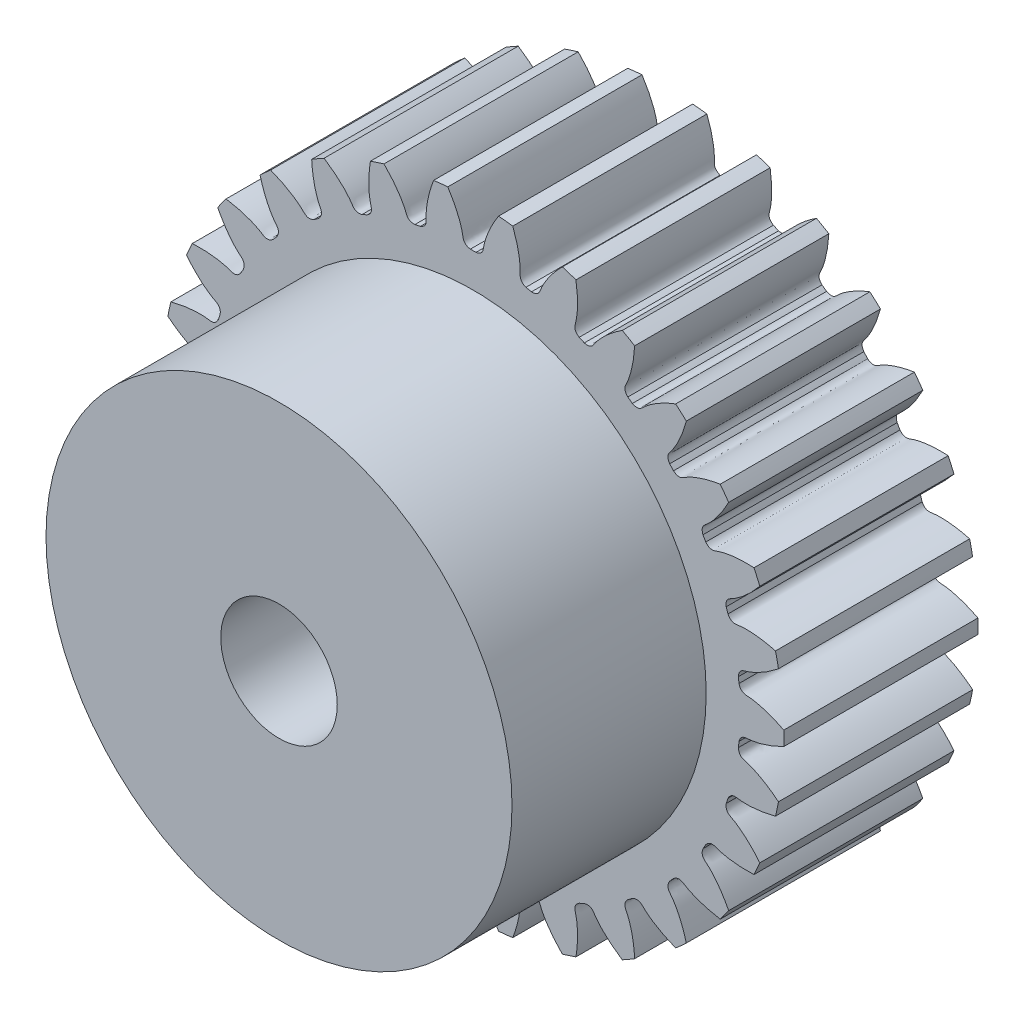
SolidWorks part; units mm, degrees
ref_plane "前视基准面" through (0, 0, 0) normal (0, 0, 1) x (1, 0, 0)
ref_plane "上视基准面" through (0, 0, 0) normal (0, 1, 0) x (1, 0, 0)
ref_plane "右视基准面" through (0, 0, 0) normal (1, 0, 0) x (0, 0, -1)
sketch "草图1" plane through (0, 0, 0) normal (0, 0, 1) x (1, 0, 0)
  circle A0 centre (0, 0) radius 8
extrude "凸台-拉伸1" add sketch "草图1" along normal blind 5
ref_axis "基准轴1" through (0, 0, 5) along (0, 0, -1)
sketch "草图2" plane through (0, 0, 0) normal (0, 0, 1) x (1, 0, 0)
  line L0 (0, 0) -> (0, 8) construction
  circle A0 centre (0, 0) radius 8 construction
  arc A1 (0.0728, 6.8746) -> (-0.0728, 6.8746) centre (0, 0) ccw
  arc A2 (1.6832, 9.0953) -> (-1.6832, 9.0953) centre (0, 0) ccw
  spline S0 degree 3 poles (0.0728, 6.8746) (0.2541, 6.9065) (0.2552, 7.0236) (0.2795, 7.1443) (0.285, 7.1691) (0.2916, 7.1965) (0.2995, 7.2264) (0.3088, 7.259) (0.3196, 7.294) (0.3319, 7.3315) (0.3459, 7.3714) (0.3617, 7.4137) (0.3794, 7.4582) (0.3991, 7.505) (0.4208, 7.554) (0.4447, 7.605) (0.4709, 7.6581) (0.4994, 7.7132) (0.5303, 7.7702) (0.5638, 7.829) (0.5999, 7.8895) (0.6387, 7.9517) (0.6803, 8.0155) (0.7247, 8.0807) (0.772, 8.1474) (0.8224, 8.2154) (0.8758, 8.2845) (0.9324, 8.3548) (0.9921, 8.4261) (1.0552, 8.4983) (1.1215, 8.5713) (1.1913, 8.6451) (1.2645, 8.7194) (1.3411, 8.7942) (1.4213, 8.8694) (1.5345, 8.9713) (1.6227, 9.046) (1.6832, 9.0953) knots 0 0 0 0 0.115324 0.123413 0.132512 0.142623 0.153745 0.165878 0.179022 0.193177 0.208343 0.22452 0.241708 0.259907 0.279117 0.299338 0.320571 0.342814 0.366068 0.390334 0.41561 0.441898 0.469196 0.497506 0.526827 0.557158 0.588501 0.620855 0.65422 0.688595 0.723982 0.76038 0.797789 0.836209 0.87564 0.916083 1 1 1 1
  spline S1 degree 3 poles (-0.0728, 6.8746) (-0.2541, 6.9065) (-0.2552, 7.0236) (-0.2795, 7.1443) (-0.285, 7.1691) (-0.2916, 7.1965) (-0.2995, 7.2264) (-0.3088, 7.259) (-0.3196, 7.294) (-0.3319, 7.3315) (-0.3459, 7.3714) (-0.3617, 7.4137) (-0.3794, 7.4582) (-0.3991, 7.505) (-0.4208, 7.554) (-0.4447, 7.605) (-0.4709, 7.6581) (-0.4994, 7.7132) (-0.5303, 7.7702) (-0.5638, 7.829) (-0.5999, 7.8895) (-0.6387, 7.9517) (-0.6803, 8.0155) (-0.7247, 8.0807) (-0.772, 8.1474) (-0.8224, 8.2154) (-0.8758, 8.2845) (-0.9324, 8.3548) (-0.9921, 8.4261) (-1.0552, 8.4983) (-1.1215, 8.5713) (-1.1913, 8.6451) (-1.2645, 8.7194) (-1.3411, 8.7942) (-1.4213, 8.8694) (-1.5345, 8.9713) (-1.6227, 9.046) (-1.6832, 9.0953) knots 0 0 0 0 0.115324 0.123413 0.132512 0.142623 0.153745 0.165878 0.179022 0.193177 0.208343 0.22452 0.241708 0.259907 0.279117 0.299338 0.320571 0.342814 0.366068 0.390334 0.41561 0.441898 0.469196 0.497506 0.526827 0.557158 0.588501 0.620855 0.65422 0.688595 0.723982 0.76038 0.797789 0.836209 0.87564 0.916083 1 1 1 1
extrude "切除-拉伸1" cut sketch "草图2" along normal through all
pattern_circular "阵列(圆周)1" count 30 every 12 about axis through (0, 0, 5) along (0, 0, -1) of "切除-拉伸1"
sketch "草图3" plane through (0, 0, 0) normal (0, 0, 1) x (1, 0, 0)
  circle A0 centre (0, 0) radius 7.5 construction
  dimension "Dn" = 15
sketch "草图5" plane through (0, 0, 5) normal (0, 0, 1) x (1, 0, 0)
  circle A0 centre (0, 0) radius 6
  dimension "D1" = 12
extrude "凸台-拉伸2" add sketch "草图5" along normal blind 5
sketch "草图6" plane through (0, 0, 10) normal (0, 0, 1) x (1, 0, 0)
  circle A0 centre (0, 0) radius 1.5
  dimension "D1" = 3
extrude "切除-拉伸3" cut sketch "草图6" against normal blind 18
